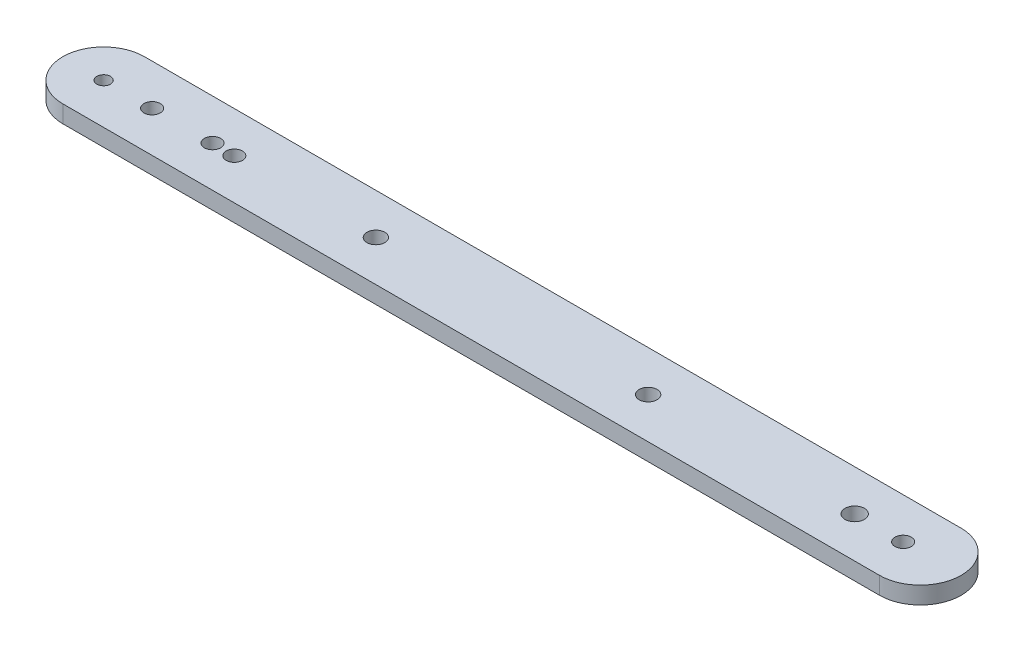
SolidWorks part; units mm, degrees
ref_plane "Front Plane" through (0, 0, 0) normal (0, 0, 1) x (1, 0, 0)
ref_plane "Top Plane" through (0, 0, 0) normal (0, 1, 0) x (1, 0, 0)
ref_plane "Right Plane" through (0, 0, 0) normal (1, 0, 0) x (0, 0, -1)
sketch "Sketch1" plane through (0, 0, 0) normal (0, 1, 0) x (1, 0, 0)
  line L0 (-82.5, 0) -> (82.5, 0) construction
  line L1 (-75, 7.5) -> (75, 7.5)
  line L3 (-75, -7.5) -> (75, -7.5)
  line L5 (-75, 7.5) -> (75, -7.5) construction
  line L6 (-75, -7.5) -> (75, 7.5) construction
  line L7 (0, 7.5) -> (0, -7.5) construction
  arc A0 (-75, 7.5) -> (-75, -7.5) centre (-75, 0) ccw
  arc A1 (75, -7.5) -> (75, 7.5) centre (75, 0) ccw
  circle A6 centre (-75, 0) radius 1.25
  circle A7 centre (-66.1, 0) radius 1.5
  circle A8 centre (-55, 0) radius 1.5
  circle A10 centre (-51, 0) radius 1.5
  circle A11 centre (71.8389, 0) radius 1.5
  circle A12 centre (62.9389, 0) radius 1.7758
  circle A13 centre (25, 0) radius 1.65
  circle A14 centre (-25, 0) radius 1.65
  point P0 (0, 0)
  dimension "D1" = 2.5
  dimension "D6" = 3
  dimension "D9" = 3.3
  dimension "D2" = 11.1
  dimension "D3" = 4
  dimension "D4" = 15
  dimension "D5" = 150
  dimension "D7" = 8.9
  dimension "D8" = 8.9
  dimension "D10" = 25
extrude "Boss-Extrude1" add sketch "Sketch1" along normal blind 3.175
